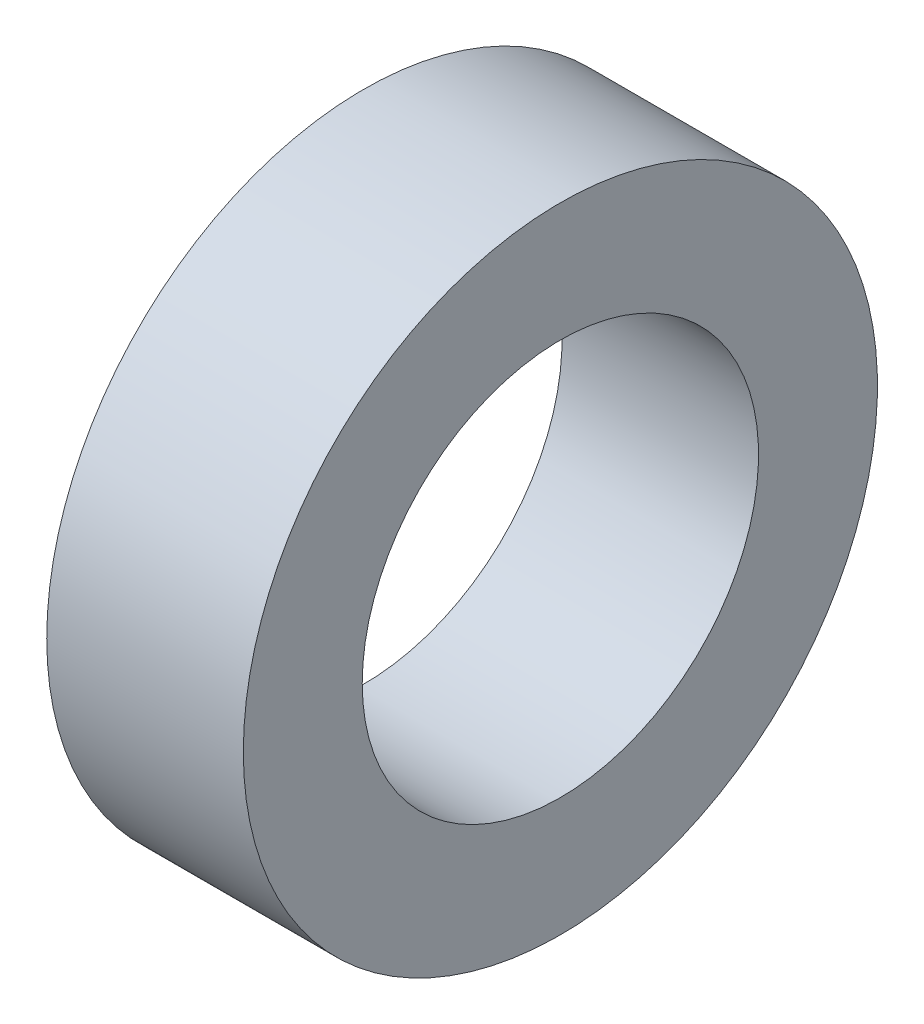
SolidWorks part; units mm, degrees
ref_plane "Front Plane" through (0, 0, 0) normal (0, 0, 1) x (1, 0, 0)
ref_plane "Top Plane" through (0, 0, 0) normal (0, 1, 0) x (1, 0, 0)
ref_plane "Right Plane" through (0, 0, 0) normal (1, 0, 0) x (0, 0, -1)
sketch "Sketch2" plane through (0, 0, 0) normal (0, 0, 1) x (1, 0, 0)
  line L0 (0, 0) -> (58.591, 0) construction
  line L2 (0, 0) -> (18.4, 0)
  line L3 (0, 0) -> (0, 2.5)
  line L4 (0, 2.5) -> (18.4, 2.5)
  line L5 (18.4, 0) -> (18.4, 2.5)
  line L6 (6.0094, 2.5) -> (6.0094, 6)
  line L11 (6.0094, 6) -> (9.9794, 6)
  line L16 (12.9794, 6) -> (12.9794, 3)
  line L17 (12.9794, 3) -> (13.6398, 3)
  line L18 (13.6398, 3) -> (13.6398, 2.5)
  line L19 (13.6398, 2.5) -> (6.0094, 2.5)
  line L22 (13.6398, 2.5) -> (16.1198, 2.5)
  line L23 (13.6398, 2.5) -> (13.6398, 4)
  line L24 (13.6398, 4) -> (16.1198, 4)
  line L25 (16.1198, 2.5) -> (16.1198, 4)
  line L27 (6.0094, 6) -> (9.9794, 6)
  line L28 (6.0094, 6) -> (6.0094, 9)
  line L29 (6.0094, 9) -> (9.9794, 9)
  line L30 (9.9794, 6) -> (9.9794, 9)
  line L31 (6.0094, 9) -> (6.0094, 8.25)
  line L32 (6.0094, 8.25) -> (5.0094, 8.25)
  line L33 (8.6609, 22.001) -> (8.6609, 12.476) construction
  line L34 (5.0094, 12.476) -> (12.3124, 12.476)
  line L35 (9.9794, 9) -> (12.3124, 9)
  line L36 (5.0094, 7.9375) -> (1.8344, 7.9375)
  line L37 (5.0094, 8.25) -> (5.0094, 12.476)
  line L38 (5.0094, 7.9375) -> (5.0094, 13.9365)
  line L39 (5.0094, 13.9365) -> (1.8344, 13.9365)
  line L40 (1.8344, 7.9375) -> (1.8344, 13.9365)
  line L41 (5.0094, 22.001) -> (12.3124, 22.001)
  line L42 (5.0094, 22.001) -> (5.0094, 30.1625)
  line L43 (5.0094, 30.1625) -> (12.3124, 30.1625)
  line L44 (12.3124, 22.001) -> (12.3124, 30.1625)
  line L49 (16.6398, 22.001) -> (16.6398, 7.5)
  line L51 (23.0198, 7.5) -> (23.0198, 6.5)
  line L54 (16.1198, 4) -> (13.6398, 4)
  line L56 (18.0398, 7.5) -> (23.0198, 7.5)
  line L57 (13.3124, 22.001) -> (16.6398, 22.001)
  line L58 (16.1198, 3.5) -> (20.0198, 3.5)
  line L59 (29.9098, 14) -> (26.9098, 11)
  line L60 (4.0094, 31.75) -> (18.0398, 31.75)
  line L61 (18.0398, 7.5) -> (23.0198, 7.5)
  line L62 (18.0398, 7.5) -> (18.0398, 12)
  line L63 (18.0398, 12) -> (23.0198, 12)
  line L64 (23.0198, 7.5) -> (23.0198, 12)
  line L65 (18.0398, 31.75) -> (18.0398, 12)
  line L66 (23.0198, 11) -> (26.9098, 11)
  line L67 (34.8098, 23) -> (31.3098, 19.5)
  line L68 (35.8098, 31) -> (38.7998, 33.99)
  line L69 (29.9098, 14) -> (29.9098, 15)
  line L70 (29.9098, 15) -> (22.9398, 15)
  line L71 (22.9398, 15) -> (21.0398, 15)
  line L72 (18.0398, 7.5) -> (16.6398, 7.5)
  line L73 (21.0398, 15) -> (21.0398, 43)
  line L74 (19.5798, 40) -> (9.6198, 40)
  line L75 (9.6198, 40) -> (4.0094, 40)
  line L76 (21.0398, 43) -> (19.5798, 43)
  line L77 (22.9398, 15) -> (29.9098, 15)
  line L78 (22.9398, 15) -> (22.9398, 21)
  line L79 (22.9398, 21) -> (29.9098, 21)
  line L80 (29.9098, 15) -> (29.9098, 21)
  line L81 (9.6198, 40) -> (19.5798, 40)
  line L82 (9.6198, 40) -> (9.6198, 50)
  line L83 (9.6198, 50) -> (19.5798, 50)
  line L84 (19.5798, 40) -> (19.5798, 50)
  line L85 (4.0094, 40) -> (4.0094, 31.75)
  line L86 (12.9794, 3) -> (12.9794, 2.5)
  line L87 (31.3098, 19.5) -> (29.9098, 19.5)
  line L88 (21.4694, 63.5) -> (21.4694, 51.308)
  line L89 (21.4694, 63.5) -> (25.9398, 63.5)
  line L90 (25.9398, 63.5) -> (25.9398, 25)
  line L91 (27.8398, 25) -> (25.9398, 25)
  line L92 (9.6198, 48) -> (8.1598, 48)
  line L93 (8.1598, 48) -> (8.1598, 53.476)
  line L94 (8.1598, 53.476) -> (19.5798, 53.476)
  line L95 (19.5798, 53.476) -> (19.5798, 50)
  line L96 (13.8698, 63.001) -> (13.8698, 53.476) construction
  line L97 (8.1598, 63.001) -> (19.5798, 63.001)
  line L98 (8.1598, 63.001) -> (8.1598, 68.2625)
  line L99 (8.1598, 68.2625) -> (19.5798, 68.2625)
  line L100 (19.5798, 63.001) -> (19.5798, 68.2625)
  line L101 (12.9794, 6) -> (11.9794, 6)
  line L102 (8.1598, 44.825) -> (4.9848, 44.825)
  line L103 (8.1598, 44.825) -> (8.1598, 54.9365)
  line L104 (8.1598, 54.9365) -> (4.9848, 54.9365)
  line L106 (9.9794, 6) -> (10.8794, 6)
  line L107 (27.8398, 25) -> (34.8098, 25)
  line L108 (34.8098, 25) -> (34.8098, 23)
  line L109 (0, 0) -> (-2, 0)
  line L110 (0, 0) -> (0, 11)
  line L111 (27.8398, 25) -> (34.8098, 25)
  line L112 (27.8398, 25) -> (27.8398, 32.5)
  line L113 (27.8398, 32.5) -> (34.8098, 32.5)
  line L114 (34.8098, 25) -> (34.8098, 32.5)
  line L115 (35.8098, 31) -> (34.8098, 31)
  line L116 (27.8398, 32.5) -> (27.8398, 64.5)
  line L117 (20.5373, 74.025) -> (6.2023, 74.025)
  line L118 (6.2023, 74.025) -> (6.2023, 76.2)
  line L119 (38.7998, 47.29) -> (30.8398, 55.25)
  line L120 (0, 11) -> (-2, 11)
  line L121 (38.7998, 43.815) -> (30.8623, 43.815)
  line L123 (-4.8152, 69.85) -> (1.5348, 76.2)
  line L124 (38.7998, 47.29) -> (38.7998, 33.99)
  line L125 (-2, 0) -> (-2, 11)
  line L126 (38.7998, 37.465) -> (30.8623, 37.465)
  line L127 (30.8623, 43.815) -> (30.8623, 37.465)
  line L128 (6.0094, 2.5) -> (6.0094, 0)
  line L129 (-0.0152, 63.5) -> (-0.0152, 30)
  line L132 (4.9848, 63.5) -> (-0.0152, 63.5)
  line L136 (-1.8152, 30) -> (-11.7752, 30)
  line L138 (-13.7752, 25.4) -> (-2, 25.4)
  line L139 (-2, 25.4) -> (-2, 11.5)
  line L140 (27.8398, 64.5) -> (20.5373, 64.5)
  line L141 (-1.8152, 30) -> (-11.7752, 30)
  line L142 (-1.8152, 30) -> (-1.8152, 39)
  line L143 (-1.8152, 39) -> (-11.7752, 39)
  line L144 (-11.7752, 30) -> (-11.7752, 39)
  line L145 (20.5373, 64.5) -> (20.5373, 74.025)
  line L146 (-12.7752, 37) -> (-12.7752, 47.29)
  line L147 (-12.7752, 37) -> (-11.7752, 37)
  line L148 (30.8398, 55.25) -> (30.8398, 76.2)
  line L149 (11.9794, 6) -> (11.9794, 5.45)
  line L154 (-2, 11.5) -> (0.5, 11.5)
  line L155 (4.9848, 60.6197) -> (24.0348, 60.6197)
  line L160 (4.9848, 60.6197) -> (4.9848, 55.8572)
  line L161 (4.9848, 55.8572) -> (24.0348, 55.8572)
  line L166 (24.0348, 60.6197) -> (24.0348, 55.8572)
  line L167 (4.9848, 60.6197) -> (24.0348, 55.8572) construction
  line L172 (4.9848, 55.8572) -> (24.0348, 60.6197) construction
  line L173 (24.0348, 62.2072) -> (25.9398, 62.2072)
  line L174 (11.9794, 5.45) -> (10.8794, 5.45)
  line L175 (10.8794, 6) -> (10.8794, 5.45)
  line L176 (24.0348, 62.2072) -> (24.0348, 54.2697)
  line L177 (24.0348, 54.2697) -> (25.9398, 54.2697)
  line L178 (25.9398, 62.2072) -> (25.9398, 54.2697)
  line L179 (24.0348, 62.2072) -> (25.9398, 54.2697) construction
  line L180 (24.0348, 54.2697) -> (25.9398, 62.2072) construction
  line L181 (3, 19.6197) -> (15.7, 19.6197)
  line L182 (3, 19.6197) -> (3, 14.8572)
  line L183 (3, 14.8572) -> (15.7, 14.8572)
  line L184 (15.7, 19.6197) -> (15.7, 14.8572)
  line L185 (3, 19.6197) -> (15.7, 14.8572) construction
  line L186 (3, 14.8572) -> (15.7, 19.6197) construction
  line L187 (15.7, 21.2072) -> (16.6398, 21.2072)
  line L188 (15.7, 21.2072) -> (15.7, 13.2697)
  line L189 (15.7, 13.2697) -> (16.6398, 13.2697)
  line L190 (16.6398, 21.2072) -> (16.6398, 13.2697)
  line L191 (15.7, 21.2072) -> (16.6398, 13.2697) construction
  line L192 (15.7, 13.2697) -> (16.6398, 21.2072) construction
  line L193 (0.5, 11.5) -> (0.5, 6.9375)
  line L194 (0.5, 6.9375) -> (1.8344, 6.9375)
  line L195 (23.0198, 6.5) -> (20.0198, 3.5)
  line L196 (4.9848, 63.5) -> (4.9848, 54.9365)
  line L197 (3, 43.825) -> (4.9848, 43.825)
  line L198 (1.8344, 6.9375) -> (1.8344, 7.9375)
  line L199 (6.0094, 0) -> (12.9794, 0)
  line L200 (12.9794, 0) -> (12.9794, 2.5)
  line L201 (18.0398, 31.75) -> (18.0398, 35.875)
  line L202 (18.0398, 35.875) -> (21.0398, 35.875)
  line L203 (30.8398, 76.2) -> (6.2023, 76.2)
  line L204 (2.7573, 69.85) -> (7.2023, 69.85) construction
  line L205 (7.2023, 67.4688) -> (26.2523, 67.4688)
  line L206 (7.2023, 74.025) -> (7.2023, 64.5)
  line L207 (7.2023, 64.5) -> (-1.8152, 64.5)
  line L208 (-1.8152, 64.5) -> (-1.8152, 39)
  line L209 (-12.7752, 47.29) -> (-4.8152, 55.25)
  line L210 (-4.8152, 55.25) -> (-4.8152, 69.85)
  line L211 (7.2023, 67.4688) -> (7.2023, 72.2312)
  line L212 (7.2023, 72.2312) -> (26.2523, 72.2313)
  line L213 (26.2523, 67.4688) -> (26.2523, 72.2313)
  line L214 (26.2523, 73.8187) -> (30.8398, 73.8187)
  line L215 (26.2523, 73.8187) -> (26.2523, 65.8813)
  line L216 (26.2523, 65.8813) -> (30.8398, 65.8813)
  line L217 (30.8398, 73.8187) -> (30.8398, 65.8813)
  line L218 (2.7573, 72.2313) -> (24.9823, 72.2313)
  line L219 (2.7573, 72.2313) -> (2.7573, 67.4687)
  line L220 (2.7573, 67.4687) -> (24.9823, 67.4687)
  line L221 (24.9823, 72.2313) -> (24.9823, 67.4687)
  line L222 (24.9823, 69.85) -> (20.5373, 69.85) construction
  line L223 (21.4694, 51.308) -> (22.9398, 51.308)
  line L224 (22.9398, 51.308) -> (22.9398, 21)
  line L225 (13.6398, 4) -> (13.6398, 12.2697)
  line L226 (13.6398, 12.2697) -> (13.3124, 12.2697)
  line L227 (13.3124, 12.2697) -> (13.3124, 22.001)
  line L228 (12.3124, 9) -> (12.3124, 12.476)
  line L229 (-1.8152, 30) -> (-0.0152, 30)
  line L230 (8.1598, 65.6317) -> (2.7573, 65.6317) construction
  line L231 (19.5798, 65.6317) -> (24.9823, 65.6317) construction
  line L232 (1.5348, 76.2) -> (6.2023, 76.2)
  line L233 (-11.7752, 30) -> (-13.7752, 30)
  line L234 (-13.7752, 30) -> (-13.7752, 25.4)
  line L235 (3, 13.9365) -> (3, 43.825)
  line L236 (4.9848, 54.9365) -> (4.9848, 44.825)
  line L237 (4.9848, 43.825) -> (4.9848, 44.825)
  circle A0 centre (26.8898, 25.95) radius 0.95
  circle A1 centre (21.9898, 15.95) radius 0.95
  circle A2 centre (17.3398, 8.2) radius 0.7
  circle A3 centre (10.4294, 6.45) radius 0.45
  circle A4 centre (-0.9152, 30.9) radius 0.9
  point P7 (24.9873, 58.2385)
  point P131 (16.1699, 17.2385)
  point P135 (14.5098, 58.2385)
  point P146 (9.35, 17.2385)
sketch "Sketch3" plane through (0, 0, 0) normal (0, 0, 1) x (1, 0, 0)
  line L0 (0, 2.5) -> (18.4, 2.5) construction
  line L1 (16.1198, 2.5) -> (16.1198, 4) construction
  line L2 (13.6398, 4) -> (16.1198, 4) construction
  line L3 (13.6398, 2.5) -> (13.6398, 4) construction
  line L4 (13.6398, 2.5) -> (16.1198, 2.5)
  line L5 (16.1198, 2.5) -> (16.1198, 4)
  line L6 (13.6398, 4) -> (16.1198, 4)
  line L7 (13.6398, 2.5) -> (13.6398, 4)
revolve "Revolve1" add sketch "Sketch3" angle 360 about L0
